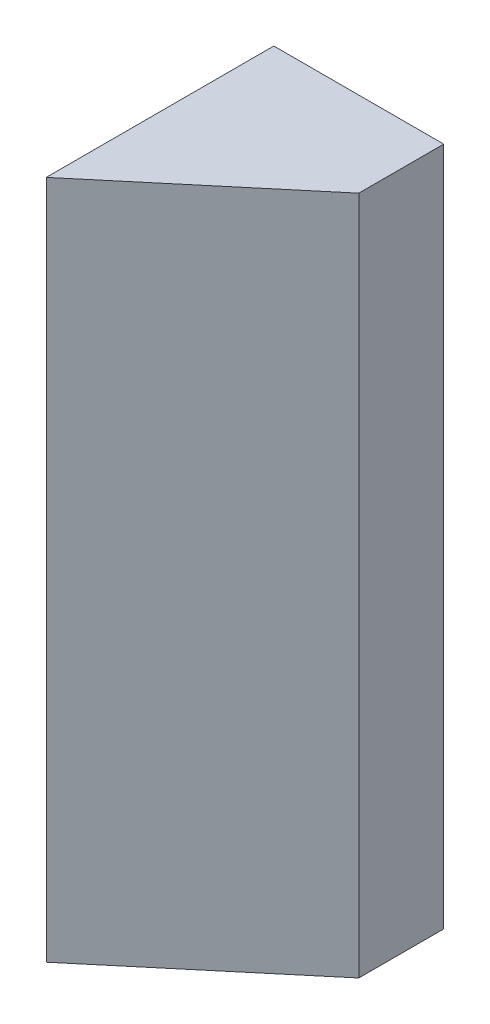
SolidWorks part; units mm, degrees
ref_plane "Front Plane" through (0, 0, 0) normal (0, 0, 1) x (1, 0, 0)
ref_plane "Top Plane" through (0, 0, 0) normal (0, 1, 0) x (1, 0, 0)
ref_plane "Right Plane" through (0, 0, 0) normal (1, 0, 0) x (0, 0, -1)
sketch "Sketch1" plane through (0, 0, 0) normal (0, 0, 1) x (1, 0, 0)
  line L1 (-3.175, 12.7) -> (3.175, 12.7)
  line L2 (-3.175, 12.7) -> (-3.175, -12.7)
  line L3 (-3.175, -12.7) -> (3.175, -12.7)
  line L4 (3.175, 12.7) -> (3.175, -12.7)
  line L5 (-3.175, 12.7) -> (3.175, -12.7) construction
  line L6 (-3.175, -12.7) -> (3.175, 12.7) construction
  point P0 (0, 0)
  dimension "D1" = 25.4
  dimension "D2" = 6.35
extrude "Boss-Extrude1" add sketch "Sketch1" along normal blind 3.175
sketch "Sketch2" plane through (0, 12.7, 0) normal (0, 1, 0) x (1, 0, 0)
  line L0 (-3.175, -3.175) -> (-3.175, -8.5033)
  line L1 (-3.175, -8.5033) -> (3.175, -3.175)
  line L2 (3.175, -3.175) -> (-3.175, -3.175)
  dimension "D1" = 40
extrude "Boss-Extrude2" add sketch "Sketch2" against normal up to surface (25.4 mm away) up to face at (0, -12.7, 1.5875)
sketch "Sketch3" plane through (0, 0, 0) normal (0, 0, -1) x (-1, 0, 0)
  line L0 (0, 12.7) -> (0, -12.7) construction
  line L1 (-3.175, 12.7) -> (3.175, 12.7) construction
  line L2 (3.175, -12.7) -> (-3.175, -12.7) construction
  circle A0 centre (0, 4.2333) radius 1.5875
  circle A1 centre (0, -4.2333) radius 1.5875
  dimension "D1" = 3.175
  dimension "D2" = 3.175
  dimension "D3" = 8.4667
  dimension "D4" = 16.9333
extrude "Cut-Extrude1" cut sketch "Sketch3" against normal blind 3.175
